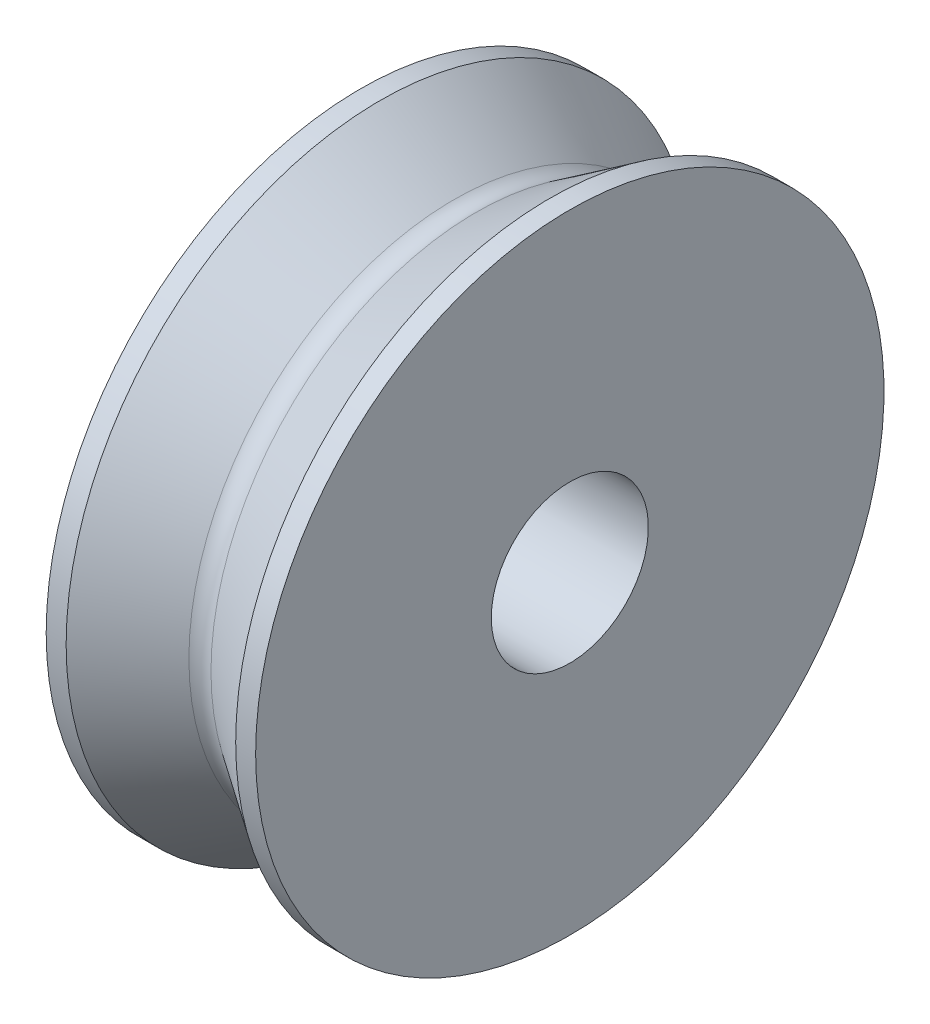
SolidWorks part; units mm, degrees
ref_plane "Front Plane" through (0, 0, 0) normal (0, 0, 1) x (1, 0, 0)
ref_plane "Top Plane" through (0, 0, 0) normal (0, 1, 0) x (1, 0, 0)
ref_plane "Right Plane" through (0, 0, 0) normal (1, 0, 0) x (0, 0, -1)
sketch "Sketch1" plane through (0, 0, 0) normal (0, 0, 1) x (1, 0, 0)
  line L0 (0, 0) -> (4, 0)
  line L1 (4, 0) -> (4, 4.5)
  line L2 (0, 4.5) -> (0, 0)
  line L3 (0, 0) -> (0, -1.5) construction
  line L4 (0, -1.5) -> (4, -1.5) construction
  line L5 (4, -1.5) -> (4, 0) construction
  line L6 (0, 4.5) -> (0.381, 4.5)
  line L7 (0.381, 4.5) -> (1.789, 3.5637)
  line L8 (2.211, 3.5637) -> (3.619, 4.5)
  line L9 (3.619, 4.5) -> (4, 4.5)
  arc A3 (1.789, 3.5637) -> (2.211, 3.5637) centre (2, 3.881) ccw
  point P8 (2, 3.5)
  point P10 (0, 4.5)
  dimension "D1" = 0.381
  dimension "D6" = 0.381
  dimension "D2" = 4
  dimension "D3" = 1.5
  dimension "D4" = 6
  dimension "D5" = 5
revolve "Revolve1" add sketch "Sketch1" angle 360 about L4
